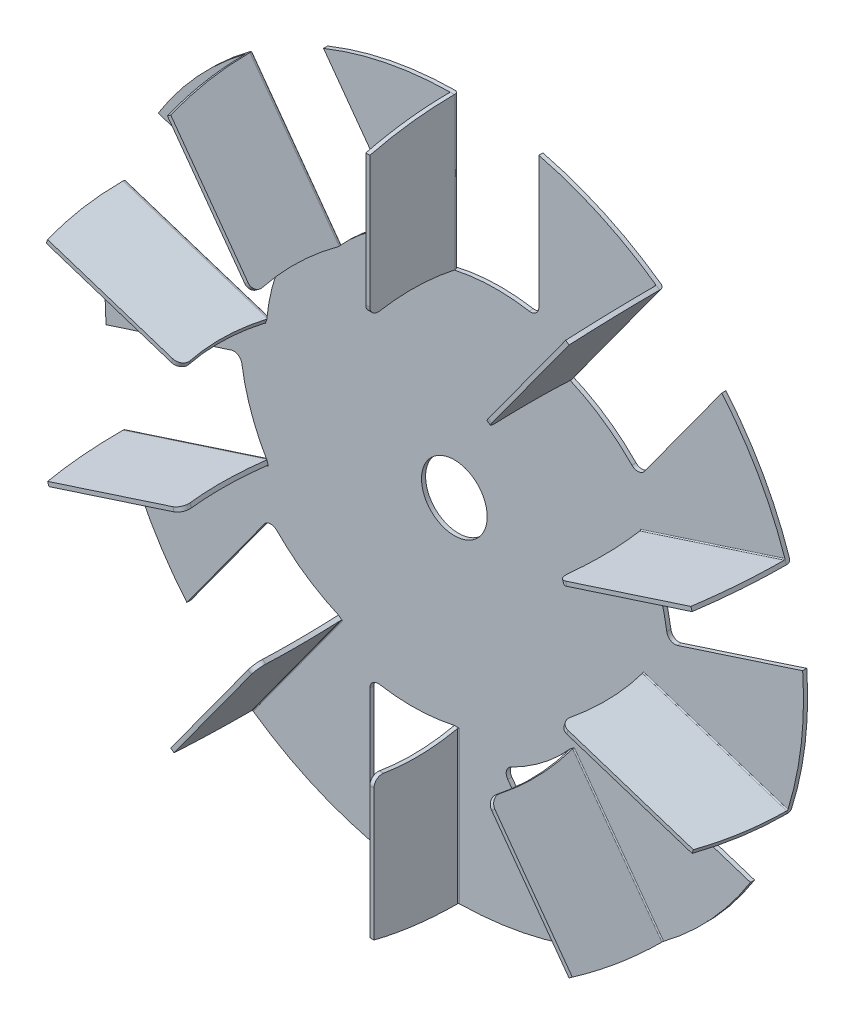
SolidWorks part; units mm, degrees
ref_plane "Front Plane" through (0, 0, 0) normal (0, 0, 1) x (1, 0, 0)
ref_plane "Top Plane" through (0, 0, 0) normal (0, 1, 0) x (1, 0, 0)
ref_plane "Right Plane" through (0, 0, 0) normal (1, 0, 0) x (0, 0, -1)
sketch "Sketch1" plane through (0, 0, 0) normal (0, 0, 1) x (1, 0, 0)
  line L1 (0, 0) -> (-19.8706, 49.1814) construction
  line L2 (0, 0) -> (30.6848, 42.234) construction
  line L3 (0, 0) -> (49.649, 16.1319) construction
  line L4 (0, 0) -> (49.649, -16.1319) construction
  line L5 (0, 0) -> (30.6848, -42.234) construction
  line L6 (0, 0) -> (0, -52.204) construction
  line L7 (0, 0) -> (-30.6848, -42.234) construction
  line L8 (0, 0) -> (-49.649, -16.1319) construction
  line L9 (0, 0) -> (-49.649, 16.1319) construction
  line L10 (0, 0) -> (-30.6848, 42.234) construction
  line L11 (-15.9208, 39.4053) -> (-5.7888, 25.4598)
  line L12 (0, 42.5) -> (0, 24)
  line L13 (-14.1068, 19.4164) -> (-24.9809, 34.3832)
  line L14 (0, 24) -> (0, 42.5)
  line L15 (10.2817, 41.2376) -> (10.2817, 24)
  line L16 (14.1068, 19.4164) -> (24.9809, 34.3832)
  line L17 (32.5569, 27.3185) -> (22.4249, 13.373)
  line L18 (22.8254, 7.4164) -> (40.4199, 13.1332)
  line L19 (42.3965, 2.9647) -> (26.0026, -2.3621)
  line L20 (22.8254, -7.4164) -> (40.4199, -13.1332)
  line L21 (36.042, -22.5216) -> (19.6481, -17.1949)
  line L22 (14.1068, -19.4164) -> (24.9809, -34.3832)
  line L23 (15.9208, -39.4053) -> (5.7888, -25.4598)
  line L24 (0, -24) -> (0, -42.5)
  line L25 (-10.2817, -41.2376) -> (-10.2817, -24)
  line L26 (-14.1068, -19.4164) -> (-24.9809, -34.3832)
  line L27 (-32.5569, -27.3185) -> (-22.4249, -13.373)
  line L28 (-22.8254, -7.4164) -> (-40.4199, -13.1332)
  line L29 (-42.3965, -2.9647) -> (-26.0026, 2.3621)
  line L30 (-22.8254, 7.4164) -> (-40.4199, 13.1332)
  line L31 (-36.042, 22.5216) -> (-19.6481, 17.1949)
  arc A0 (-24.9809, 34.3832) -> (-36.042, 22.5216) centre (0, 0) ccw
  circle A1 centre (0, 0) radius 24 construction
  arc A2 (0, 42.5) -> (-15.9208, 39.4053) centre (0, 0) ccw
  arc A3 (-14.1068, 19.4164) -> (-5.7888, 25.4598) centre (3.7335, 3.6073) cw
  arc A4 (24.9809, 34.3832) -> (10.2817, 41.2376) centre (0, 0) ccw
  arc A5 (0, 24) -> (10.2817, 24) centre (5.1408, 0.7239) cw
  arc A6 (-40.4199, 13.1332) -> (-42.3965, -2.9647) centre (0, 0) ccw
  arc A7 (14.1068, 19.4164) -> (22.4249, 13.373) centre (4.5845, -2.4361) cw
  arc A8 (40.4199, 13.1332) -> (32.5569, 27.3185) centre (0, 0) ccw
  arc A9 (22.8254, 7.4164) -> (26.0026, -2.3621) centre (2.2771, -4.6655) cw
  arc A10 (40.4199, -13.1332) -> (42.3965, 2.9647) centre (0, 0) ccw
  arc A11 (22.8254, -7.4164) -> (19.6481, -17.1949) centre (-0.9002, -5.1129) cw
  arc A12 (24.9809, -34.3832) -> (36.042, -22.5216) centre (0, 0) ccw
  arc A13 (14.1068, -19.4164) -> (5.7888, -25.4598) centre (-3.7335, -3.6073) cw
  arc A14 (0, -42.5) -> (15.9208, -39.4053) centre (0, 0) ccw
  arc A15 (0, -24) -> (-10.2817, -24) centre (-5.1408, -0.7239) cw
  arc A16 (-24.9809, -34.3832) -> (-10.2817, -41.2376) centre (0, 0) ccw
  arc A17 (-14.1068, -19.4164) -> (-22.4249, -13.373) centre (-4.5845, 2.4361) cw
  circle A18 centre (0, 0) radius 4
  arc A19 (-22.8254, -7.4164) -> (-26.0026, 2.3621) centre (-2.2771, 4.6655) cw
  arc A20 (-40.4199, -13.1332) -> (-32.5569, -27.3185) centre (0, 0) ccw
  arc A21 (-22.8254, 7.4164) -> (-19.6481, 17.1949) centre (0.9002, 5.1129) cw
  point P17 (0, 0)
  point P71 (0, 0)
  dimension "D5" = 10
extrude "Boss-Extrude1" add sketch "Sketch1" along normal blind 0.5 contours A21 L30 A6 L29 A19 L28 A20 L27 A17 L26 A16 L25 A15 L24 A14 L23 A13 L22 A12 L21 A11 L20 A10 L19 A9 L18 A8 L17 A7 L16 A4 L15 A5 L12 A2 L11 A3 L13 A0 L31 A18 region at (-7.88, 40.5392, 0)
sketch "Sketch2" plane through (0, 0, 0.5) normal (0, 0, 1) x (1, 0, 0)
  line L0 (0, 42.5) -> (0, 24) construction
  line L1 (10.2817, 41.2376) -> (10.2817, 24) construction
  line L2 (0, 42.5) -> (0, 24)
  line L3 (10.2817, 41.2376) -> (10.2817, 24)
  arc A0 (10.2817, 24) -> (0, 24) centre (5.1408, 0.7239) ccw construction
  arc A1 (10.2817, 24) -> (0, 24) centre (5.1408, 0.7239) ccw
  arc A2 (0, 42.5) -> (10.2817, 41.2376) centre (0, 0) cw
  arc A3 (24.9809, 34.3832) -> (10.2817, 41.2376) centre (0, 0) ccw construction
ref_axis "Axis1" through (0, 0, 10.433) along (0, 0, -1)
sketch "Sketch3" plane through (0, 0, 0) normal (1, 0, 0) x (0, 0, -1)
  line L0 (-0.5, 42.5) -> (-0.5, 24)
  line L2 (-0.5, 24) -> (-0.5, 49.9385) construction
  line L3 (-10.7817, 41.2376) -> (-10.7817, 24)
  arc A1 (-10.7817, 41.2376) -> (-0.5, 42.5) centre (-0.5, 0) cw
  arc A2 (-10.7817, 24) -> (-0.5, 24) centre (-5.6408, 0.7239) cw
extrude "Boss-Extrude2" add sketch "Sketch3" against normal blind 0.5
pattern_circular "CirPattern1" count 10 over 360 about axis through (0, 0, 10.433) along (0, 0, -1) of "Boss-Extrude2"
fillet "Fillet1" radius 1 10 edges at (-26.0026, 2.3621, 0.25) (-22.4249, -13.373, 0.25) (-10.2817, -24, 0.25) (5.7888, -25.4598, 0.25) (19.6481, -17.1949, 0.25) (26.0026, -2.3621, 0.25) (22.4249, 13.373, 0.25) (10.2817, 24, 0.25) (-5.7888, 25.4598, 0.25) (-19.6481, 17.1949, 0.25)
fillet "Fillet2" radius 1 10 edges at (-13.9046, -19.5634, 10.7817) (0.25, -24, 10.7817) (14.3091, -19.2695, 10.7817) (22.9026, -7.1786, 10.7817) (22.7481, 7.6542, 10.7817) (13.9046, 19.5634, 10.7817) (-0.25, 24, 10.7817) (-14.3091, 19.2695, 10.7817) (-22.9026, 7.1786, 10.7817) (-22.7481, -7.6542, 10.7817)
fillet "Fillet3" radius 0.4 10 edges at (-31.6226, -10.2748, 0) (-19.5439, -26.8998, 0) (0, -33.25, 0) (19.5439, -26.8998, 0) (31.6226, -10.2748, 0) (31.6226, 10.2748, 0) (19.5439, 26.8998, 0) (0, 33.25, 0) (-19.5439, 26.8998, 0) (-31.6226, 10.2748, 0)
fillet "Fillet4" radius 0.125 10 edges at (-19.1385, -27.1925, 0.5) (-31.4667, -10.7499, 0.5) (-31.7757, 9.7988, 0.5) (-19.9475, 26.6047, 0.5) (-0.5, 33.2485, 0.5) (19.1385, 27.1925, 0.5) (31.4667, 10.7499, 0.5) (31.7757, -9.7988, 0.5) (19.9475, -26.6047, 0.5) (0.5, -33.2485, 0.5)
